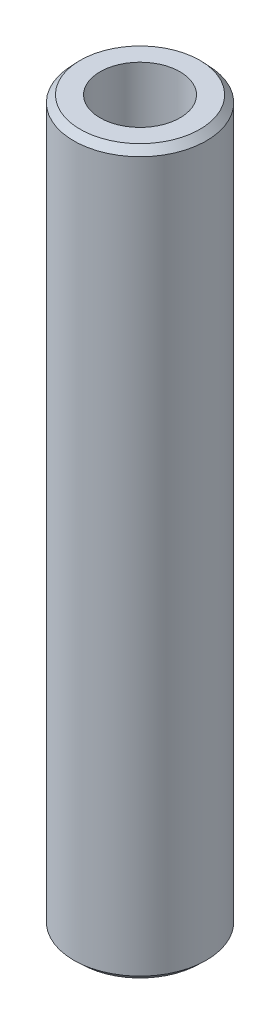
SolidWorks part; units mm, degrees
ref_plane "Front Plane" through (0, 0, 0) normal (0, 0, 1) x (1, 0, 0)
ref_plane "Top Plane" through (0, 0, 0) normal (0, 1, 0) x (1, 0, 0)
ref_plane "Right Plane" through (0, 0, 0) normal (1, 0, 0) x (0, 0, -1)
sketch "Sketch1" plane through (0, 0, 0) normal (0, 1, 0) x (1, 0, 0)
  circle A0 centre (0, 0) radius 55
  dimension "SHAFT_OD" = 110
extrude "Boss-Extrude1" add sketch "Sketch1" along normal blind 600
sketch "Sketch2" plane through (0, 0, 0) normal (0, 1, 0) x (1, 0, 0)
  circle A0 centre (0, 0) radius 33.177
  dimension "BORE_D" = 66.3539
extrude "Cut-Extrude1" cut sketch "Sketch2" along normal through all
chamfer "Chamfer1" distance 5.6437 angle 43.401 2 edges at (0, 600, 55) (0, 0, 55) first distance on face at (0, 600, 55) first distance on face at (0, 0, 33.177)
